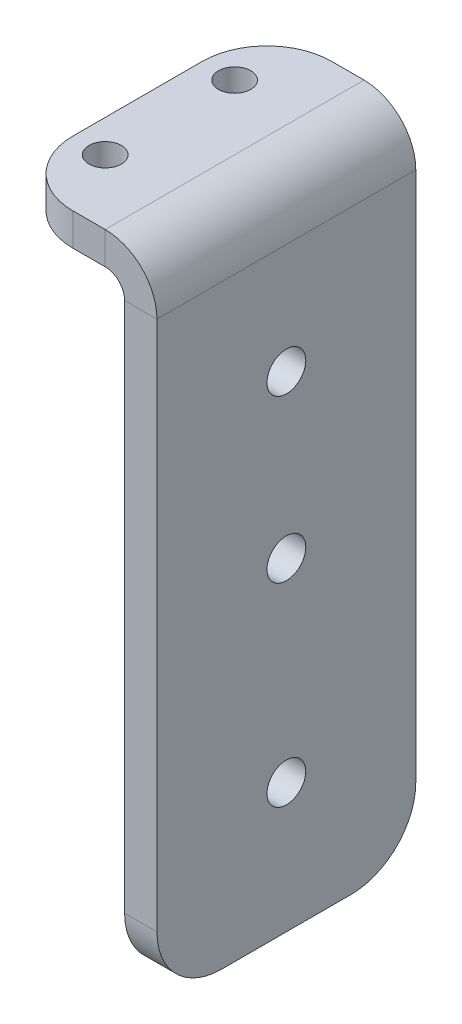
SolidWorks part; units mm, degrees
note: The reader was unsure of these and kept them because the rebuilt part matched: flange length of "Edge-Flange1".
ref_plane "Front Plane" through (0, 0, 0) normal (0, 0, 1) x (1, 0, 0)
ref_plane "Top Plane" through (0, 0, 0) normal (0, 1, 0) x (1, 0, 0)
ref_plane "Right Plane" through (0, 0, 0) normal (1, 0, 0) x (0, 0, -1)
sketch "Sketch1" plane through (0, 0, 0) normal (1, 0, 0) x (0, 0, -1)
  line L1 (-20, 50) -> (20, 50)
  line L2 (-20, 50) -> (-20, -50)
  line L3 (-20, -50) -> (20, -50)
  line L4 (20, 50) -> (20, -50)
  line L5 (-20, 50) -> (20, -50) construction
  line L6 (-20, -50) -> (20, 50) construction
  point P0 (0, 0)
  dimension "D1" = 100
  dimension "D2" = 40
base flange "Base-Flange1" sketch "Sketch1" thickness 5 reverse thickness direction no parameters "D1"=3
edge flange "Edge-Flange1" sketch "Sketch8" flange angle 90 flange length 18 flange position material inside bend radius 3 thickness 5 relief rectangular parameters "D1"=5, "D6"=10
sketch "Sketch8" plane through (-5, 50, 0) normal (0, -1, 0) x (0, 0, 1)
  line L2 (-20, 0) -> (-20, 18)
  line L3 (-20, 18) -> (20, 18)
  line L4 (20, 18) -> (20, 0)
  line L5 (20, 0) -> (-20, 0) construction
  line L6 (20, 0) -> (-20, 0)
bend "EdgeBend1" bend radius 3 bend angle 90 parameters "D5"=1
sketch "Sketch9" plane through (0, 50, 0) normal (0, 1, 0) x (1, 0, 0)
  line L0 (0, 20) -> (0, -20) construction
  circle A0 centre (-18, 10) radius 2.5
  circle A1 centre (-18, -10) radius 2.5
  dimension "D1" = 5
  dimension "D2" = 5
  dimension "D3" = 18
  dimension "D4" = 10
  dimension "D5" = 10
extrude "Cut-Extrude1" cut sketch "Sketch9" against normal blind 10
fillet "Fillet1" radius 10 4 edges at (-2.5, -50, -20) (-2.5, -50, 20) (-23, 47.5, 20) (-23, 47.5, -20)
sketch "Sketch16" plane through (0, 0, 0) normal (1, 0, 0) x (0, 0, -1)
  line L0 (0, 0) -> (0, -30) construction
  line L1 (0, 0) -> (0, 25) construction
  circle A0 centre (0, 0) radius 3
  circle A1 centre (0, -30) radius 3
  circle A2 centre (0, 25) radius 3
  dimension "D1" = 6
  dimension "D3" = 30
  dimension "D5" = 25
  dimension "D2" = 2
  dimension "D4" = 2
extrude "Cut-Extrude2" cut sketch "Sketch16" against normal blind 10
sketch "Bend-Lines1" [suppressed] plane through (0, 0, 0) normal (0, 1, 0) x (1, 0, 0)
sketch "Bounding-Box1" [suppressed] plane through (0, 0, 0) normal (0, 1, 0) x (1, 0, 0)
sheet metal parameters "Sheet-Metal1" thickness 5 parameters "D1"=2
flat pattern "Flat-Pattern1" [suppressed]
sketch "Bend-Lines2" plane through (0, 0, 0) normal (0, 1, 0) x (1, 0, 0)
sketch3d "Bounding-Box2" [suppressed]
  line L0 (-20, 50, 0) -> (-20, -50, 0) construction
  line L1 (20, 50, 0) -> (20, -50, 0) construction
  line L2 (-20, 50, 0) -> (20, 50, 0) construction
  line L3 (-20, -50, 0) -> (20, -50, 0) construction
sheet metal parameters "Sheet-Metal2" thickness 5 parameters "D1"=2
flat pattern "Flat-Pattern1"
sketch "Bend-Lines2" plane through (0, 0, 0) normal (1, 0, 0) x (0, 0, -1)
  line L0 (20, 46.2594) -> (-20, 46.2594) construction
  line L1 (20, 46.2594) -> (-20, 46.2594) construction
sketch3d "Bounding-Box2" [suppressed]
  line L0 (20, 67.5188, 0) -> (20, -50, 0) construction
  line L1 (-20, 67.5188, 0) -> (-20, -50, 0) construction
  line L2 (20, 67.5188, 0) -> (-20, 67.5188, 0) construction
  line L3 (20, -50, 0) -> (-20, -50, 0) construction
bend of the flat pattern "Flatten-<EdgeBend1>1"
sheet metal parameters "Sheet-Metal3" thickness 5 parameters "D1"=2
flat pattern "Flat-Pattern1" [suppressed]
sketch "Bend-Lines2" plane through (0, 0, 0) normal (1, 0, 0) x (0, 0, -1)
  line L0 (20, 45.6156) -> (-20, 45.6156) construction
  line L1 (20, 45.6156) -> (-20, 45.6156) construction
sketch3d "Bounding-Box2" [suppressed]
  line L0 (20, 64.2312, 0) -> (20, -50, 0) construction
  line L1 (-20, 64.2312, 0) -> (-20, -50, 0) construction
  line L2 (20, 64.2312, 0) -> (-20, 64.2312, 0) construction
  line L3 (20, -50, 0) -> (-20, -50, 0) construction
bend of the flat pattern "Flatten-<EdgeBend1>1"
sketch "Sketch13-1" plane through (-5, 41.2312, 0) normal (-1, 0, 0) x (0, 1, 0)
  ellipse E1 centre (6.9289, 0) end of major axis (-1.5563, 0) minor radius 6 (10, -5.5932) -> (10, 5.5932) ccw
sketch "Sketch15-1" plane through (-5, 0, 0) normal (-1, 0, 0) x (0, 0, 1)
  ellipse E1 centre (0, 43.0711) end of major axis (0, 34.5858) minor radius 6 (-5.5932, 40) -> (5.5932, 40) ccw
sheet metal parameters "Sheet-Metal4" thickness 5 parameters "D1"=2
flat pattern "Flat-Pattern1"
sketch "Bend-Lines2" plane through (0, 0, 0) normal (1, 0, 0) x (0, 0, -1)
  line L0 (20, 46.0448) -> (-20, 46.0448) construction
  line L1 (20, 46.0448) -> (-20, 46.0448) construction
sketch3d "Bounding-Box2" [suppressed]
  line L0 (20, 65.0896, 0) -> (20, -50, 0) construction
  line L1 (-20, 65.0896, 0) -> (-20, -50, 0) construction
  line L2 (20, 65.0896, 0) -> (-20, 65.0896, 0) construction
  line L3 (20, -50, 0) -> (-20, -50, 0) construction
bend of the flat pattern "Flatten-<EdgeBend1>1"
